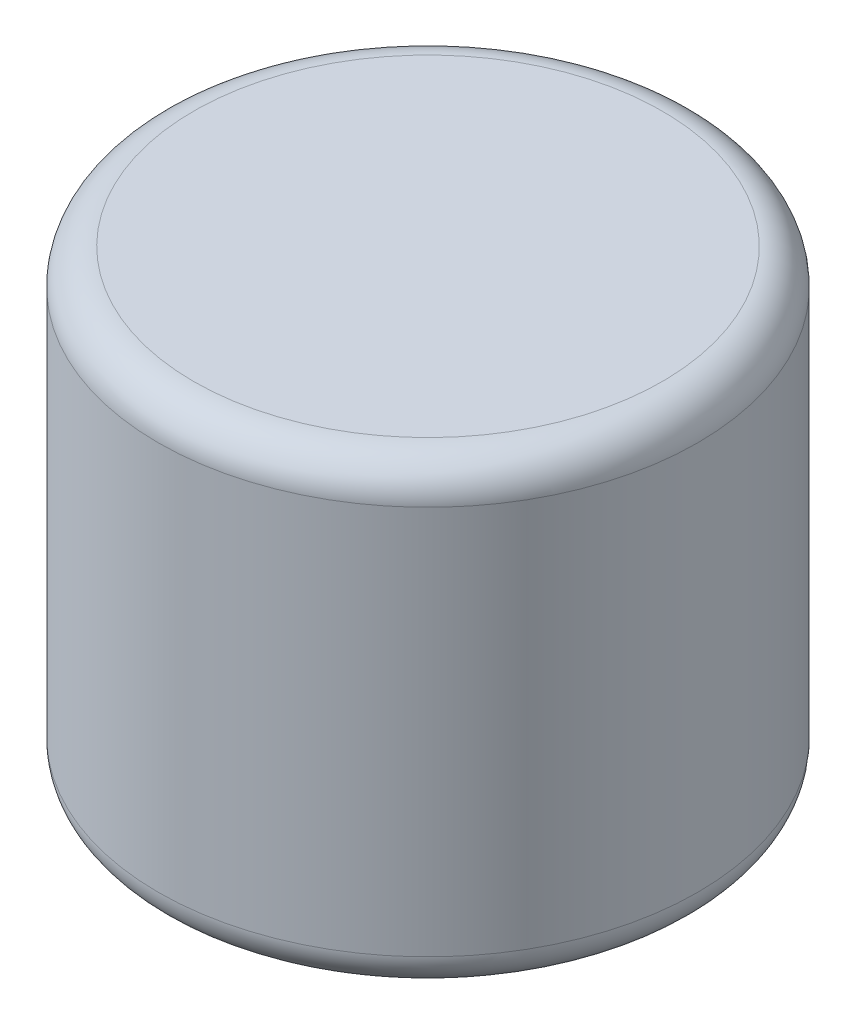
SolidWorks part; units mm, degrees
ref_plane "Front Plane" through (0, 0, 0) normal (0, 0, 1) x (1, 0, 0)
ref_plane "Top Plane" through (0, 0, 0) normal (0, 1, 0) x (1, 0, 0)
ref_plane "Right Plane" through (0, 0, 0) normal (1, 0, 0) x (0, 0, -1)
sketch "Sketch1" plane through (0, 0, 0) normal (0, 1, 0) x (1, 0, 0)
  circle A0 centre (0, 0) radius 76.2
  dimension "D1" = 152.4
extrude "Boss-Extrude1" add sketch "Sketch1" along normal blind 130
fillet "Fillet3" radius 10 2 edges at (0, 0, 76.2) (0, 130, 76.2)
